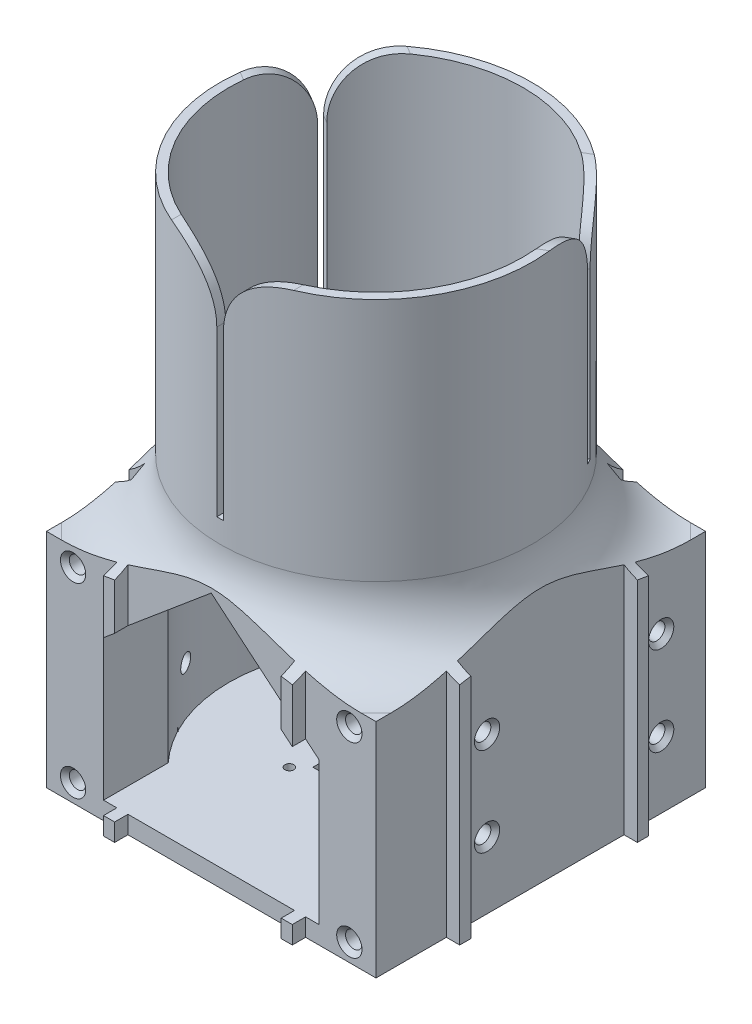
SolidWorks part; units mm, degrees
ref_plane "Front Plane" through (0, 0, 0) normal (0, 0, 1) x (1, 0, 0)
ref_plane "Top Plane" through (0, 0, 0) normal (0, 1, 0) x (1, 0, 0)
ref_plane "Right Plane" through (0, 0, 0) normal (1, 0, 0) x (0, 0, -1)
sketch "Sketch1" plane through (0, 0, 0) normal (0, 1, 0) x (1, 0, 0)
  line L0 (7.1, -7.1) -> (7.1, 7.1)
  line L1 (7.1, -7.1) -> (-7.1, -7.1)
  line L2 (7.1, 7.1) -> (-7.1, 7.1)
  line L3 (-7.1, -7.1) -> (-7.1, 7.1)
  line L4 (7.1, -7.1) -> (-7.1, 7.1) construction
  line L5 (7.1, 7.1) -> (-7.1, -7.1) construction
  line L6 (37.1, -37.1) -> (37.1, -21.25)
  line L7 (37.1, -37.1) -> (21.25, -37.1)
  line L8 (37.1, 37.1) -> (21.5, 37.1)
  line L9 (-37.1, -37.1) -> (-37.1, -21.5)
  line L10 (37.1, -37.1) -> (-37.1, 37.1) construction
  line L11 (37.1, 37.1) -> (-37.1, -37.1) construction
  line L12 (37.1, 21.25) -> (40.1, 21.25)
  line L13 (40.1, 21.25) -> (40.1, 18.75)
  line L14 (40.1, 18.75) -> (37.1, 18.75)
  line L15 (21.25, 0) -> (30.6436, 0) construction
  line L16 (40.1, -18.75) -> (37.1, -18.75)
  line L17 (40.1, -21.25) -> (40.1, -18.75)
  line L18 (37.1, -21.25) -> (40.1, -21.25)
  line L19 (37.1, 21.25) -> (37.1, 37.1)
  line L20 (37.1, -18.75) -> (37.1, 18.75)
  line L21 (21.25, -37.1) -> (21.25, -40.1)
  line L22 (21.25, -40.1) -> (18.75, -40.1)
  line L23 (18.75, -40.1) -> (18.75, -37.1)
  line L24 (18.75, -37.1) -> (-18.75, -37.1)
  line L25 (-37.1, -18.5) -> (-33.6, -18.5)
  line L26 (-33.6, -18.5) -> (-33.6, -21.5)
  line L27 (-33.6, -21.5) -> (-37.1, -21.5)
  line L28 (21.5, 37.1) -> (21.5, 33.6)
  line L29 (21.5, 33.6) -> (18.5, 33.6)
  line L30 (18.5, 33.6) -> (18.5, 37.1)
  line L31 (18.5, 37.1) -> (-18.5, 37.1)
  line L32 (-37.1, -18.5) -> (-37.1, 18.5)
  line L33 (-33.6, 21.5) -> (-37.1, 21.5)
  line L34 (-33.6, 18.5) -> (-33.6, 21.5)
  line L35 (-37.1, 18.5) -> (-33.6, 18.5)
  line L36 (-37.1, 21.5) -> (-37.1, 37.1)
  line L37 (0, 0) -> (0, 18.7785) construction
  line L38 (-18.75, -40.1) -> (-18.75, -37.1)
  line L39 (-21.25, -40.1) -> (-18.75, -40.1)
  line L40 (-21.25, -37.1) -> (-21.25, -40.1)
  line L41 (-21.5, 37.1) -> (-21.5, 33.6)
  line L42 (-21.5, 33.6) -> (-18.5, 33.6)
  line L43 (-18.5, 33.6) -> (-18.5, 37.1)
  line L44 (-21.25, -37.1) -> (-37.1, -37.1)
  line L45 (-21.5, 37.1) -> (-37.1, 37.1)
  circle A0 centre (0, 0) radius 33.1
  circle A2 centre (-9.751, 9.751) radius 1
  circle A3 centre (9.751, 9.751) radius 1
  circle A4 centre (9.751, -9.751) radius 1
  circle A5 centre (-9.751, -9.751) radius 1
  point P1 (0, 0)
  point P2 (0, 0)
  point P34 (0, 0)
  point P36 (20, -40.1)
  point P38 (40.1, -20)
  point P50 (40.1, 20)
  point P51 (-33.6, 20)
  point P53 (20, 33.6)
  dimension "D3" = 66.2
  dimension "D8" = 2
  dimension "D1" = 14.2
  dimension "D2" = 4
  dimension "D4" = 2.5
  dimension "D6" = 3
  dimension "D7" = 13.79
  dimension "D10" = 20
  dimension "D11" = 3
  dimension "D12" = 3.5
  dimension "D13" = 4
  dimension "D5" = 20
  dimension "D9" = 4
extrude "Boss-Extrude1" add sketch "Sketch1" along normal blind 4 contours L16 L20 L14 L13 L12 L19 L8 L9 L7 L6 L18 L17 A0 | A0 L1 L3 L2 L0 region at (29.175, 0, 36.0082) region at (-32.1638, 0, 0)
extrude "Boss-Extrude2" add sketch "Sketch1<4>" along normal blind 50 contours L16 L20 L14 L13 L12 L19 L8 L9 L7 L6 L18 L17 A0 region at (29.175, 0, 36.0082)
sketch "Sketch1<4>" plane through (0, 0, 0) normal (0, 1, 0) x (1, 0, 0) same geometry as "Sketch1"
sketch "Sketch12" plane through (0, 50, 0) normal (0, 1, 0) x (1, 0, 0)
  circle A0 centre (0, 0) radius 33.1
  circle A1 centre (0, 0) radius 35.1
  dimension "D1" = 66.2
  dimension "D2" = 2
extrude "Boss-Extrude3" add sketch "Sketch12" along normal blind 70
fillet "Fillet2" radius 15 1 edges at (0, 50, 35.1)
sketch "Sketch9" plane through (0, 120, 0) normal (0, 1, 0) x (1, 0, 0)
  line L0 (0, 0) -> (37.922, 21.8943) construction
  line L1 (0, 0) -> (0, -43.7885) construction
  line L2 (0, 0) -> (-37.922, 21.8943) construction
  line L3 (0.75, -0.433) -> (0.75, -43.7885)
  line L4 (-0.75, -0.433) -> (-38.297, 21.2447)
  line L5 (0, 0.866) -> (37.547, 22.5438)
  line L6 (-0.75, -0.433) -> (-0.75, -43.7885)
  line L7 (0, 0.866) -> (-37.547, 22.5438)
  line L8 (0.75, -0.433) -> (38.297, 21.2447)
  line L9 (-37.547, 22.5438) -> (-38.297, 21.2447)
  line L10 (37.547, 22.5438) -> (38.297, 21.2447)
  line L11 (-0.75, -43.7885) -> (0.75, -43.7885)
  line L12 (-0.375, 0.6495) -> (37.547, 22.5438) construction
  line L13 (0.375, 0.6495) -> (-37.547, 22.5438) construction
  line L14 (0.75, 0) -> (0.75, -43.7885) construction
  line L15 (0.375, -0.6495) -> (38.297, 21.2447) construction
  line L16 (-0.375, -0.6495) -> (-38.297, 21.2447) construction
  line L17 (-0.75, 0) -> (-0.75, -43.7885) construction
  dimension "D1" = 120
  dimension "D2" = 120
  dimension "D3" = 1.5
extrude "Cut-Extrude2" cut sketch "Sketch9" against normal blind 50 and the other way blind 50
sketch "Sketch13" plane through (0, 0, -37.1) normal (0, 0, -1) x (-1, 0, 0)
  line L0 (-37.1, 51.9215) -> (-37.1, 0) construction
  line L1 (-37.1, 0) -> (-21.5, 0) construction
  line L2 (-33.669, 50) -> (-37.1, 50) construction
  line L3 (37.1, 50) -> (37.1, 0) construction
  line L4 (33.6, 0) -> (33.6, 28.0835) construction
  line L5 (21.5, 0) -> (37.1, 0) construction
  circle A0 centre (-31.1, 4) radius 1.85
  circle A1 centre (31.1, 4) radius 1.85
  circle A2 centre (31.1, 46) radius 1.85
  circle A3 centre (-31.1, 46) radius 1.85
  dimension "D1" = 3.7
  dimension "D2" = 6
  dimension "D3" = 4
  dimension "D4" = 4
  dimension "D5" = 6
  dimension "D6" = 3.5
extrude "Cut-Extrude3" cut sketch "Sketch13" against normal blind 22
ref_plane "Plane1" through (0, 0, 0) normal (0, 0, -1) x (-1, 0, 0)
mirror "Mirror3" about plane through (0, 0, 0) normal (0, 0, -1) of "Cut-Extrude3"
chamfer "Chamfer1" distance 1 angle 45 8 edges at (29.25, 46, -37.1) (29.25, 4, -37.1) (-32.95, 46, -37.1) (-32.95, 4, -37.1) (29.25, 4, 37.1) (29.25, 46, 37.1) (-32.95, 46, 37.1) (-32.95, 4, 37.1)
sketch "Sketch14" plane through (0, 0, -37.1) normal (0, 0, -1) x (-1, 0, 0)
  line L0 (0, 0) -> (0, 57.5167) construction
  line L3 (24.25, 36.1685) -> (0, 56.5167)
  line L4 (-24.25, 36.1685) -> (0, 56.5167)
  line L8 (24.25, 36.1685) -> (24.25, 4)
  line L9 (24.25, 4) -> (-24.25, 4)
  line L10 (-24.25, 4) -> (-24.25, 36.1685)
  line L11 (-24.25, 36.1685) -> (0, 36.1685) construction
  line L12 (-18.5, 0) -> (18.5, 0) construction
  circle A1 centre (-31.1, 4) radius 2.85 construction
  spline S0 degree 3 poles (18.5, 52.7406) (16.9749, 53.2204) (15.46, 53.7353) (12.4322, 54.7728) (10.9197, 55.2963) (7.8698, 56.2565) (6.3324, 56.6936) (3.9748, 57.1704) (3.1802, 57.299) (1.5673, 57.4738) (0.7658, 57.5178) (-0.8263, 57.5155) (-1.6169, 57.4694) (-3.1885, 57.2971) (-3.9696, 57.1711) (-6.3017, 56.7005) (-7.845, 56.2638) (-10.904, 55.3017) (-12.4192, 54.7773) (-15.4526, 53.7378) (-16.9705, 53.2218) (-18.5, 52.7406) knots 0 0 0 0 0.125 0.125 0.25 0.25 0.375 0.375 0.4375 0.4375 0.5 0.5 0.5625 0.5625 0.625 0.625 0.75 0.75 0.875 0.875 1 1 1 1 construction
  dimension "D4" = 4
  dimension "D1" = 40
  dimension "D2" = 4
  dimension "D3" = 1
extrude "Cut-Extrude4" cut sketch "Sketch14" against normal blind 177
fillet "Fillet3" radius 10 2 edges at (-24.25, 36.1685, -29.8144) (24.25, 36.1685, -29.8144)
fillet "Fillet5" radius 13 6 edges at (-29.8993, 120, -16.3964) (-29.1493, 120, -17.6954) (29.1493, 120, -17.6954) (29.8993, 120, -16.3964) (0.75, 120, 34.0917) (-0.75, 120, 34.0917)
sketch "Sketch15" plane through (37.1, 0, 0) normal (1, 0, 0) x (0, 0, -1)
  line L0 (-37.1, 25) -> (37.1, 25) construction
  line L1 (-37.1, 50) -> (-37.1, 0) construction
  line L2 (37.1, 50) -> (37.1, 0) construction
  circle A0 centre (27.1, 35) radius 1.85
  circle A1 centre (27.1, 15) radius 1.85
  circle A3 centre (-12.1, 15) radius 1.85
  circle A4 centre (-12.1, 35) radius 1.85
  point P14 (-8.4307, 35)
  point P15 (0, 0)
  point P16 (0, 0)
  point P17 (0, 0)
  dimension "D1" = 3.7
  dimension "D2" = 20
  dimension "D3" = 39.2
  dimension "D4" = 10
extrude "Cut-Extrude5" cut sketch "Sketch15" against normal up to surface (74.2 mm away) up to face at (-37.1, 30.5556, -28.9569)
chamfer "Chamfer2" distance 1 angle 45 8 edges at (-37.1, 15, 13.95) (-37.1, 15, -25.25) (-37.1, 35, -25.25) (37.1, 15, 10.25) (37.1, 35, -28.95) (37.1, 15, -28.95) (-37.1, 35, 13.95) (37.1, 35, 10.25)
equation "\"CanDiameter\"=40.6328"
equation "\"D11@Sketch1\"=\"D4@Sketch1\"+.5"
equation "\"D12@Sketch1\"=\"D6@Sketch1\"+.5"
equation "\"D5@Sketch1\"=\"D10@Sketch1\""
